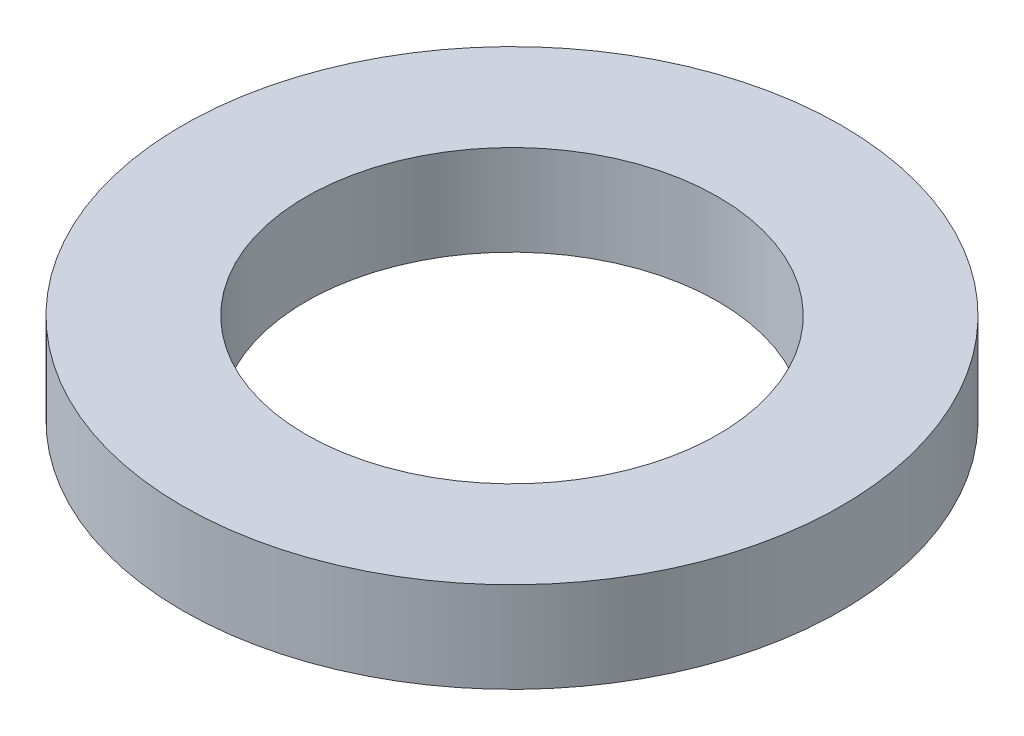
SolidWorks part; units mm, degrees
ref_plane "Front Plane" through (0, 0, 0) normal (0, 0, 1) x (1, 0, 0)
ref_plane "Top Plane" through (0, 0, 0) normal (0, 1, 0) x (1, 0, 0)
ref_plane "Right Plane" through (0, 0, 0) normal (1, 0, 0) x (0, 0, -1)
sketch "Sketch1" plane through (0, 0, 0) normal (0, 1, 0) x (1, 0, 0)
  circle A0 centre (0, 0) radius 40
  dimension "FLANGE_OD" = 80
extrude "Boss-Extrude1" add sketch "Sketch1" along normal blind 11
sketch "Sketch2" plane through (0, 0, 0) normal (0, 1, 0) x (1, 0, 0)
  circle A0 centre (0, 0) radius 25
  dimension "BORE_D" = 50
extrude "Cut-Extrude1" cut sketch "Sketch2" along normal through all
sketch "Sketch3" plane through (0, 11, 0) normal (0, 1, 0) x (1, 0, 0)
  circle A0 centre (0, 0) radius 16.1871 construction
  circle A1 centre (-16.1871, 0) radius 1.5565
  dimension "BOLT_D" = 3.113
  dimension "BOLT_PCD" = 32.3743
extrude "Cut-Extrude2" cut sketch "Sketch3" against normal blind 9.0035 rebuild error yes
pattern_circular "CirPattern1" count 3 over 360 rebuild error yes
